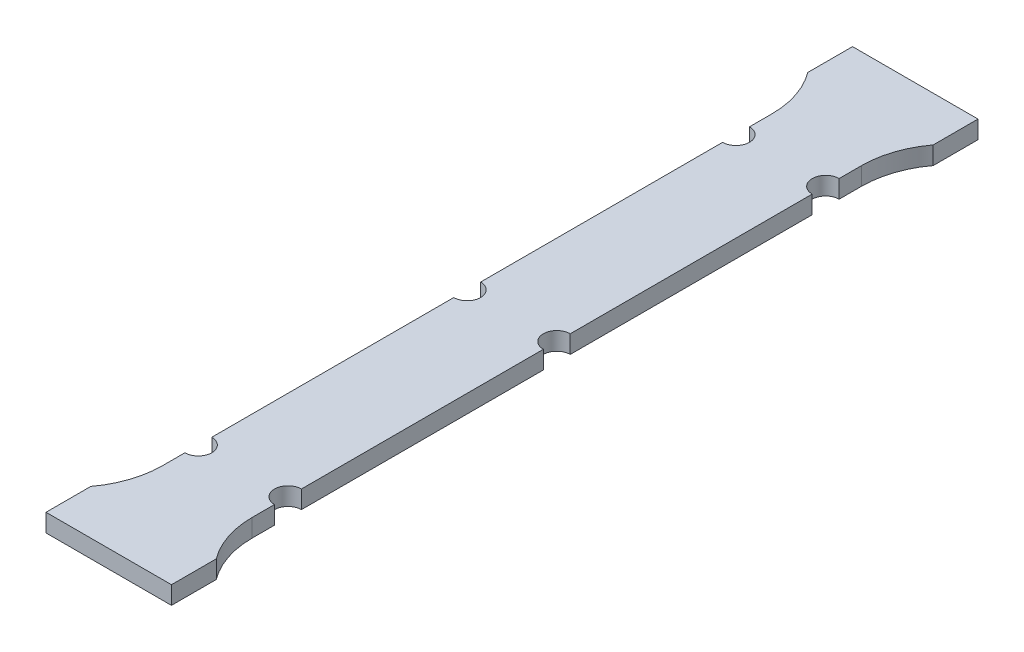
SolidWorks part; units mm, degrees
ref_plane "前视基准面" through (0, 0, 0) normal (0, 0, 1) x (1, 0, 0)
ref_plane "上视基准面" through (0, 0, 0) normal (0, 1, 0) x (1, 0, 0)
ref_plane "右视基准面" through (0, 0, 0) normal (1, 0, 0) x (0, 0, -1)
other "Configuration Table"
sketch "草图1" plane through (0, 0, 0) normal (0, 1, 0) x (1, 0, 0)
  line L0 (0, 0) -> (0, -90)
  line L1 (0, -90) -> (10, -90)
  line L2 (10, -90) -> (10, 0)
  line L3 (10, 0) -> (0, 0)
  line L4 (10, -45) -> (0, -45)
  line L5 (5, -45) -> (7.5, -45)
  line L6 (7.5, -45) -> (7.5, -42.5)
  line L7 (7.5, -42.5) -> (2.5, -42.5)
  line L8 (2.5, -42.5) -> (2.5, -47.5)
  line L9 (2.5, -47.5) -> (7.5, -47.5)
  line L10 (7.5, -47.5) -> (7.5, -45)
  line L19 (10, -90) -> (12, -90)
  line L20 (12, -90) -> (12, -85)
  line L21 (12, -85) -> (10, -85)
  line L22 (10, -85) -> (10, -90)
  line L23 (0, -90) -> (-2, -90)
  line L24 (-2, -90) -> (-2, -85)
  line L25 (-2, -85) -> (0, -85)
  line L26 (0, -85) -> (0, -90)
  line L35 (0, 0) -> (-2, 0)
  line L36 (-2, 0) -> (-2, -5)
  line L37 (-2, -5) -> (0, -5)
  line L38 (10, 0) -> (12, 0)
  line L39 (12, 0) -> (12, -5)
  line L40 (12, -5) -> (10, -5)
  line L41 (10, -5) -> (10, 0)
  line L42 (0, 0) -> (0, -5)
  circle A0 centre (10, -45) radius 1.5
  circle A2 centre (10, -15) radius 1.5
  circle A4 centre (0, -15) radius 1.5
  circle A14 centre (0, -45) radius 1.5
  circle A15 centre (0, -75) radius 1.5
  circle A17 centre (10, -75) radius 1.5
  circle A20 centre (0, -45) radius 1.5
  dimension "D1" = 2
  dimension "D6" = 10
  dimension "D11" = 90
  dimension "D12" = 5
  dimension "D13" = 2
  dimension "D2" = 2
  dimension "D3" = 2
  dimension "D4" = 2
extrude "凸台-拉伸1" add sketch "草图1" along normal blind 2
fillet "圆角1" radius 10 4 edges at (10, 1, 85) (0, 1, 85) (0, 1, 5) (10, 1, 5)
